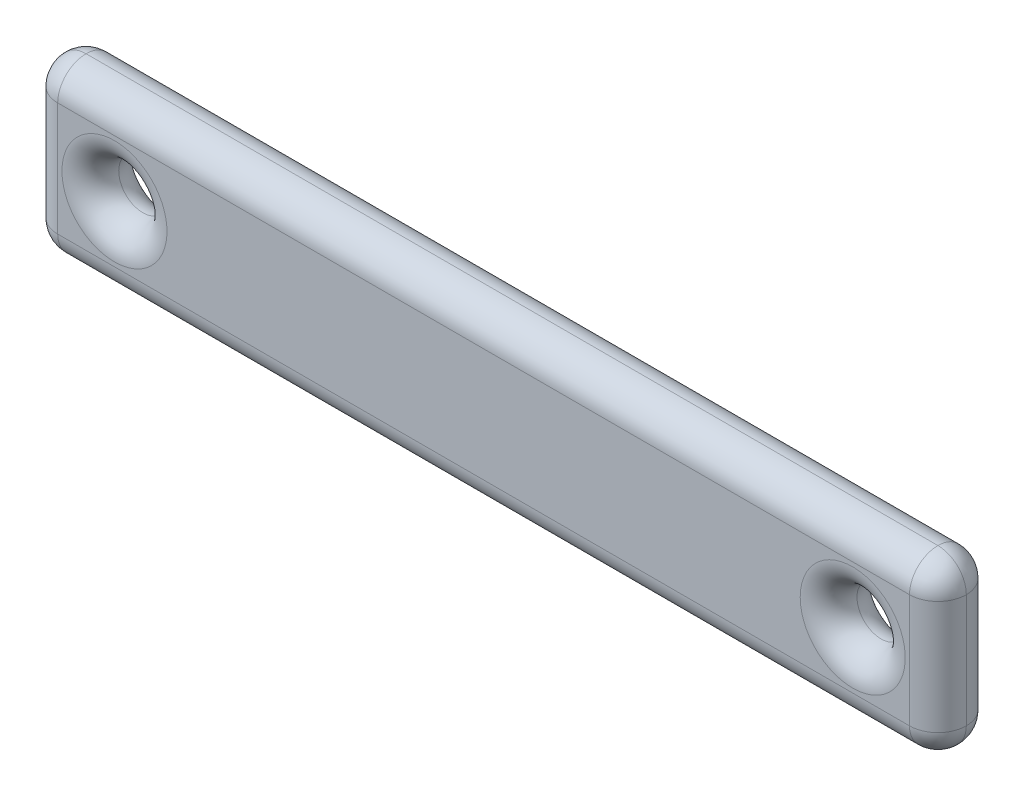
SolidWorks part; units mm, degrees
ref_plane "前视基准面" through (0, 0, 0) normal (0, 0, 1) x (1, 0, 0)
ref_plane "上视基准面" through (0, 0, 0) normal (0, 1, 0) x (1, 0, 0)
ref_plane "右视基准面" through (0, 0, 0) normal (1, 0, 0) x (0, 0, -1)
other "Configuration Table"
sketch "草图1" plane through (0, 0, 0) normal (0, 0, 1) x (1, 0, 0)
  line L1 (-6, -6) -> (58, -6)
  line L2 (-6, -6) -> (-6, 6)
  line L3 (-6, 6) -> (58, 6)
  line L4 (58, -6) -> (58, 6)
  line L5 (-6, -6) -> (58, 6) construction
  line L6 (-6, 6) -> (58, -6) construction
  circle A0 centre (0, 0) radius 1.7
  circle A1 centre (52, 0) radius 1.7
  point P0 (26, 0)
extrude "凸台-拉伸1" add sketch "草图1" along normal mid plane 4
fillet "圆角1" radius 2 12 edges at (53.7, 0, -2) (53.7, 0, 2) (1.7, 0, -2) (1.7, 0, 2) (58, 0, -2) (26, 6, -2) (-6, 0, -2) (26, -6, -2) (58, 0, 2) (26, 6, 2) (-6, 0, 2) (26, -6, 2) tangent propagation no
